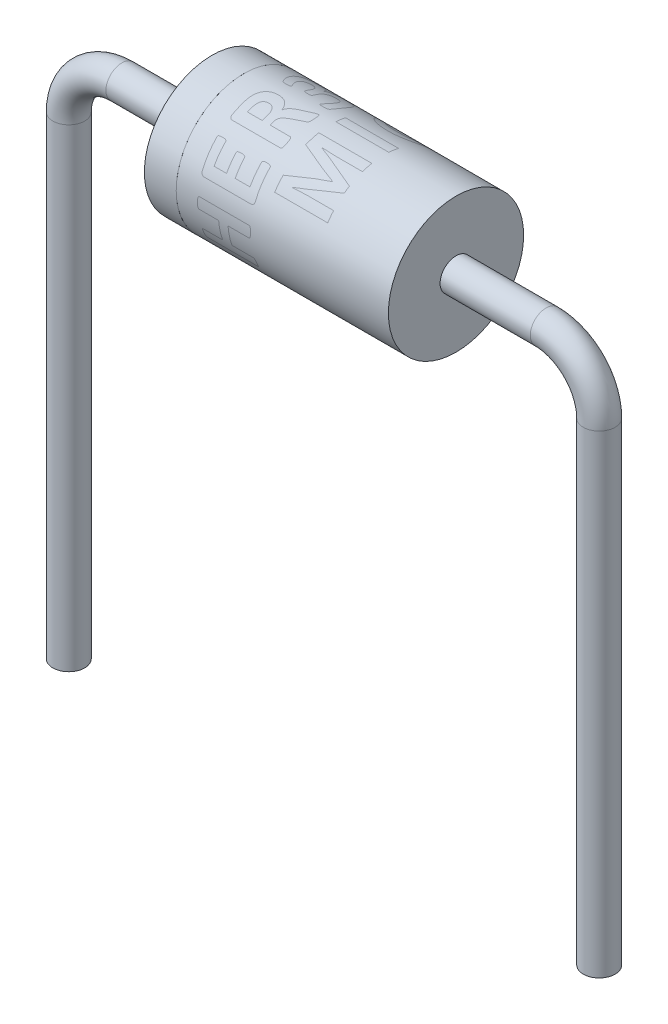
SolidWorks part; units mm, degrees
other "Wire"
other "Cathode Silver Band"
other "Diode"
ref_plane "Front Plane" through (0, 0, 0) normal (0, 0, 1) x (1, 0, 0)
ref_plane "Top Plane" through (0, 0, 0) normal (0, 1, 0) x (1, 0, 0)
ref_plane "Right Plane" through (0, 0, 0) normal (1, 0, 0) x (0, 0, -1)
sketch "Sketch1" plane through (0, 0, 0) normal (1, 0, 0) x (0, 0, -1)
  circle A0 centre (0, 0) radius 2.55
  circle A1 centre (0, 0) radius 0.6
  dimension "D1" = 5.1
  dimension "D2" = 1.2
extrude "Boss-Extrude1" add sketch "Sketch1" along normal mid plane 9.2
sketch "Sketch2" plane through (-4.6, 0, 0) normal (-1, 0, 0) x (0, 0, 1)
  circle A1 centre (0, 0) radius 2.55 construction
  circle A2 centre (0, 0) radius 2.54
  circle A3 centre (0, 0) radius 2.54
  circle A4 centre (0, 0) radius 2.55
  dimension "D1" = 0.01
extrude "Cut-Extrude1" cut sketch "Sketch2" against normal blind 1.2
sketch "Sketch3" plane through (-3.4, 0, 0) normal (-1, 0, 0) x (0, 0, 1)
  circle A0 centre (0, 0) radius 2.54 construction
  circle A1 centre (0, 0) radius 2.54
  circle A2 centre (0, 0) radius 2.55 construction
  circle A3 centre (0, 0) radius 2.55
extrude "Boss-Extrude2" add sketch "Sketch3" along normal up to surface (1.2 mm away) separate body up to face at (-4.6, 0, -0.6)
ref_plane "Plane1" through (0, 5, 0) normal (0, 1, 0) x (1, 0, 0)
sketch "Sketch4" plane through (0, 5, 0) normal (0, 1, 0) x (1, 0, 0)
  line L0 (-0.6, 7.5) -> (-0.6, -7.5) construction
  line L1 (-0.6, 0) -> (-4.6, 0) construction
  line L2 (-4.6, 2.55) -> (-4.6, -2.55) construction
  line L4 (-0.6, 0) -> (1.9, 0) construction
  line L5 (1.9, 7.5) -> (1.9, -7.5) construction
  text T0 "HER303" font "Calibri" height 2
  text T1 "MIC" font "Corbel" height 2
  dimension "D1" = 4
  dimension "D2" = 15
  dimension "D3" = 2.5
wrap "Wrap1" sketch "Sketch4" wrap type scribe source sketch "Sketch4" face at (4.6, 0, -2.55)
sketch "Sketch5" plane through (0, 0, 0) normal (0, 0, 1) x (1, 0, 0)
  line L0 (0, 0) -> (-8, 0)
  line L1 (-10, -2) -> (-10, -19.8584)
  line L2 (0, 0) -> (8, 0)
  line L3 (10, -2) -> (10, -19.8584)
  arc A0 (-8, 0) -> (-10, -2) centre (-8, -2) ccw
  arc A1 (8, 0) -> (10, -2) centre (8, -2) cw
  dimension "D2" = 2
  dimension "D3" = 58
  dimension "D1" = 20
sketch "Sketch6" plane through (0, 0, 0) normal (1, 0, 0) x (0, 0, -1)
  circle A0 centre (0, 0) radius 0.6
  dimension "D1" = 1.2
sweep "Sweep1" add profiles "Sketch6" path "Sketch5"
